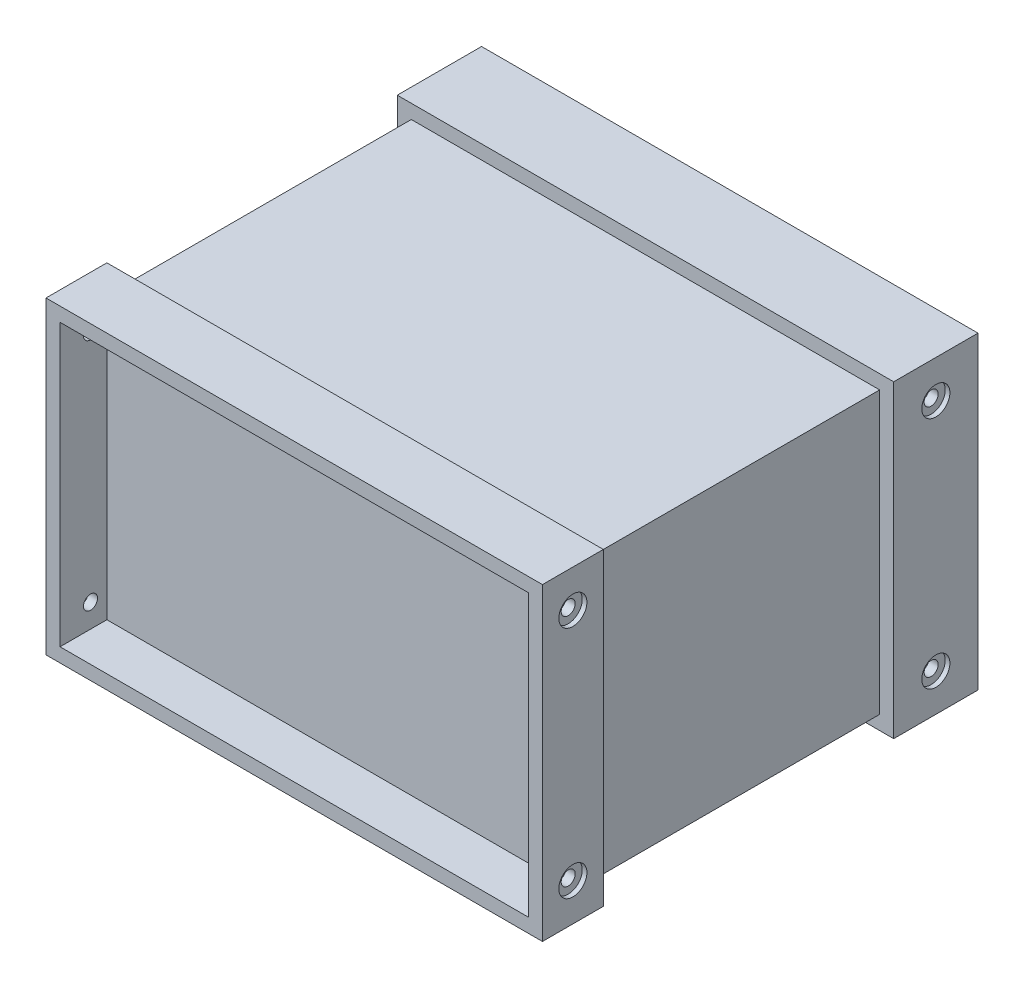
SolidWorks part; units mm, degrees
ref_plane "Front Plane" through (0, 0, 0) normal (0, 0, 1) x (1, 0, 0)
ref_plane "Top Plane" through (0, 0, 0) normal (0, 1, 0) x (1, 0, 0)
ref_plane "Right Plane" through (0, 0, 0) normal (1, 0, 0) x (0, 0, -1)
sketch "Sketch1" plane through (0, 0, 0) normal (0, 0, 1) x (1, 0, 0)
  line L1 (-40.2483, 30.9603) -> (59.7517, 30.9603)
  line L2 (-40.2483, 30.9603) -> (-40.2483, -29.0397)
  line L3 (-40.2483, -29.0397) -> (59.7517, -29.0397)
  line L4 (59.7517, 30.9603) -> (59.7517, -29.0397)
  line L5 (-37.7483, 28.4603) -> (57.2517, 28.4603)
  line L6 (-37.7483, 28.4603) -> (-37.7483, -26.5397)
  line L7 (-37.7483, -26.5397) -> (57.2517, -26.5397)
  line L8 (57.2517, 28.4603) -> (57.2517, -26.5397)
  arc A1 (-37.7483, 19.2236) -> (-28.5116, 28.4603) centre (-40.2483, 30.9603) ccw
  arc A2 (-37.7483, 21.2778) -> (-30.5659, 28.4603) centre (-40.2483, 30.9603) ccw
  arc A3 (48.015, 28.4603) -> (57.2517, 19.2236) centre (59.7517, 30.9603) ccw
  arc A4 (50.0692, 28.4603) -> (57.2517, 21.2778) centre (59.7517, 30.9603) ccw
  arc A5 (-28.5116, -26.5397) -> (-37.7483, -17.303) centre (-40.2483, -29.0397) ccw
  arc A6 (-30.5659, -26.5397) -> (-37.7483, -19.3573) centre (-40.2483, -29.0397) ccw
  arc A7 (57.2517, -17.303) -> (48.015, -26.5397) centre (59.7517, -29.0397) ccw
  arc A8 (57.2517, -19.3573) -> (50.0692, -26.5397) centre (59.7517, -29.0397) ccw
  dimension "D3" = 2.5
  dimension "D1" = 100
  dimension "D2" = 60
  dimension "D4" = 2.5
  dimension "D5" = 2.5
  dimension "D6" = 2.5
extrude "Boss-Extrude1" add sketch "Sketch1" along normal blind 150 contours L4 L1 L2 L3 L5 L8 L7 L6 | A2 L6 A1 L5 | A4 L5 A3 L8 | A8 L8 A7 L7 | A6 L7 A5 L6 region at (9.7517, 29.7941, 0) region at (-32.8375, 23.5494, 0) region at (52.3408, 23.5494, 0) region at (-32.8375, -21.6289, 0) region at (52.3408, -21.6289, 0)
sketch "Sketch2" plane through (0, 30.9603, 0) normal (0, 1, 0) x (1, 0, 0)
  line L1 (-37.7483, -150) -> (57.2517, -150)
  line L3 (-37.7483, -135) -> (57.2517, -135)
  line L6 (57.2517, -135) -> (-37.7483, -135)
  line L7 (57.2517, -135) -> (57.2517, -150)
  line L8 (57.2517, -150) -> (-37.7483, -150)
  line L9 (-37.7483, -135) -> (-37.7483, -150)
  line M4 (-40.2483, -150) -> (59.7517, -150)
  dimension "D1" = 15
extrude "Cut-Extrude1" cut sketch "Sketch2" against normal blind 20 contours L3 L9 L7 M4 region at (9.7517, 30.9603, 142.5)
sketch "Sketch3" plane through (0, 0, 0) normal (0, 0, -1) x (-1, 0, 0)
  line L1 (-62.7517, -32.0397) -> (43.2483, -32.0397)
  line L2 (-62.7517, -32.0397) -> (-62.7517, 33.9603)
  line L3 (-62.7517, 33.9603) -> (43.2483, 33.9603)
  line L4 (-59.7517, 30.9603) -> (-59.7517, -29.0397)
  line L5 (-59.7517, -29.0397) -> (40.2483, -29.0397)
  line L6 (40.2483, -29.0397) -> (40.2483, 30.9603)
  line L7 (40.2483, 30.9603) -> (-59.7517, 30.9603)
  line L8 (-59.7517, 30.9603) -> (-59.7517, -29.0397)
  line L9 (-59.7517, -29.0397) -> (40.2483, -29.0397)
  line L10 (40.2483, -29.0397) -> (40.2483, 30.9603)
  line L11 (40.2483, 30.9603) -> (-59.7517, 30.9603)
  line L12 (43.2483, -32.0397) -> (43.2483, 33.9603)
  dimension "D2" = 3
  dimension "D3" = 3
  dimension "D4" = 3
  dimension "D5" = 3
  dimension "D1" = 0
extrude "Boss-Extrude2" add sketch "Sketch3" along normal blind 13 and the other way blind 5
sketch "Sketch4" plane through (-43.2483, 0, 0) normal (-1, 0, 0) x (0, 0, 1)
  line L0 (5, 33.9603) -> (-13, 33.9603) construction
  circle A0 centre (-4, -24.0397) radius 1.5
  circle A1 centre (-4, 25.9603) radius 1.5
  dimension "D1" = 50
  dimension "D2" = 8
extrude "Cut-Extrude2" cut sketch "Sketch4" against normal blind 120
sketch "Sketch5" plane through (62.7517, 0, 0) normal (1, 0, 0) x (0, 0, -1)
  circle A0 centre (4, -24.0397) radius 3
  circle A1 centre (4, 25.9603) radius 3
extrude "Cut-Extrude3" cut sketch "Sketch5" against normal blind 1
sketch "Sketch6" plane through (-43.2483, 0, 0) normal (-1, 0, 0) x (0, 0, 1)
  circle A0 centre (-4, 25.9603) radius 3
  circle A1 centre (-4, -24.0877) radius 3
extrude "Cut-Extrude4" cut sketch "Sketch6" against normal blind 1
sketch "Sketch8" plane through (0, 0, 150) normal (0, 0, 1) x (1, 0, 0)
  line L1 (-55.1202, 40.6562) -> (70.7593, 40.6562)
  line L2 (-55.1202, 40.6562) -> (-55.1202, -39.7895)
  line L3 (-55.1202, -39.7895) -> (70.7593, -39.7895)
  line L4 (70.7593, 40.6562) -> (70.7593, -39.7895)
extrude "Cut-Extrude6" cut sketch "Sketch8" against normal blind 80
sketch "Sketch9" plane through (0, 0, 70) normal (0, 0, 1) x (1, 0, 0)
  line L6 (-40.2483, 30.9603) -> (59.7517, 30.9603)
  line L7 (-40.2483, 30.9603) -> (-40.2483, -29.0397)
  line L8 (-40.2483, -29.0397) -> (59.7517, -29.0397)
  line L9 (59.7517, 30.9603) -> (59.7517, -29.0397)
  line L10 (-43.2483, 33.9603) -> (62.7517, 33.9603)
  line L11 (-43.2483, 33.9603) -> (-43.2483, -32.0397)
  line L12 (-43.2483, -32.0397) -> (62.7517, -32.0397)
  line L13 (62.7517, 33.9603) -> (62.7517, -32.0397)
extrude "Boss-Extrude3" add sketch "Sketch9" along normal blind 10 and the other way blind 3
sketch "Sketch10" plane through (-43.2483, 0, 0) normal (-1, 0, 0) x (0, 0, 1)
  circle A1 centre (73.5, 25.9603) radius 1.5
  circle A3 centre (73.5, -24.0397) radius 1.5
  circle A4 centre (73.5, 25.9603) radius 3
  circle A5 centre (73.5, -24.0397) radius 3
extrude "Cut-Extrude7" cut sketch "Sketch10" against normal blind 117 contours A3 | A1
extrude "Cut-Extrude8" cut sketch "Sketch10<3>" against normal blind 1 contours A5 | A4
sketch "Sketch10<3>" plane through (-43.2483, 0, 0) normal (-1, 0, 0) x (0, 0, 1) same geometry as "Sketch10"
sketch "Sketch11" plane through (62.7517, 0, 0) normal (1, 0, 0) x (0, 0, -1)
  circle A0 centre (-73.5, -24.0397) radius 3
  circle A1 centre (-73.5, 25.9603) radius 3
extrude "Cut-Extrude9" cut sketch "Sketch11" against normal blind 1
sketch "Sketch12" plane through (0, 0, 70) normal (0, 0, 1) x (1, 0, 0)
  line L4 (-40.2483, 30.9603) -> (-40.2483, -29.0397)
  line L5 (-40.2483, -29.0397) -> (59.7517, -29.0397)
  line L6 (59.7517, -29.0397) -> (59.7517, 30.9603)
  line L7 (59.7517, 30.9603) -> (-40.2483, 30.9603)
  line L8 (-40.2483, 30.9603) -> (-40.2483, -29.0397)
  line L9 (-40.2483, -29.0397) -> (59.7517, -29.0397)
  line L10 (59.7517, -29.0397) -> (59.7517, 30.9603)
  line L11 (59.7517, 30.9603) -> (-40.2483, 30.9603)
  dimension "D1" = 0
extrude "Boss-Extrude4" add sketch "Sketch12" against normal blind 2
sketch "Sketch13" plane through (0, -29.0397, 0) normal (0, -1, 0) x (1, 0, 0)
  line L1 (49.7517, 15) -> (-30.2483, 15)
  line L3 (49.7517, 57) -> (-30.2483, 57)
  line L6 (62.7517, 5) -> (-43.2483, 5) construction
  line L8 (-43.2483, 67) -> (62.7517, 67) construction
  line L9 (49.7517, 15) -> (49.7517, 57)
  line L10 (-30.2483, 15) -> (-30.2483, 57)
  line L11 (59.7517, 67) -> (59.7517, 5) construction
  line L12 (-40.2483, 67) -> (-40.2483, 5) construction
  dimension "D1" = 10
  dimension "D2" = 10
  dimension "D3" = 10
  dimension "D4" = 10
extrude "Cut-Extrude10" cut sketch "Sketch13" against normal blind 10
